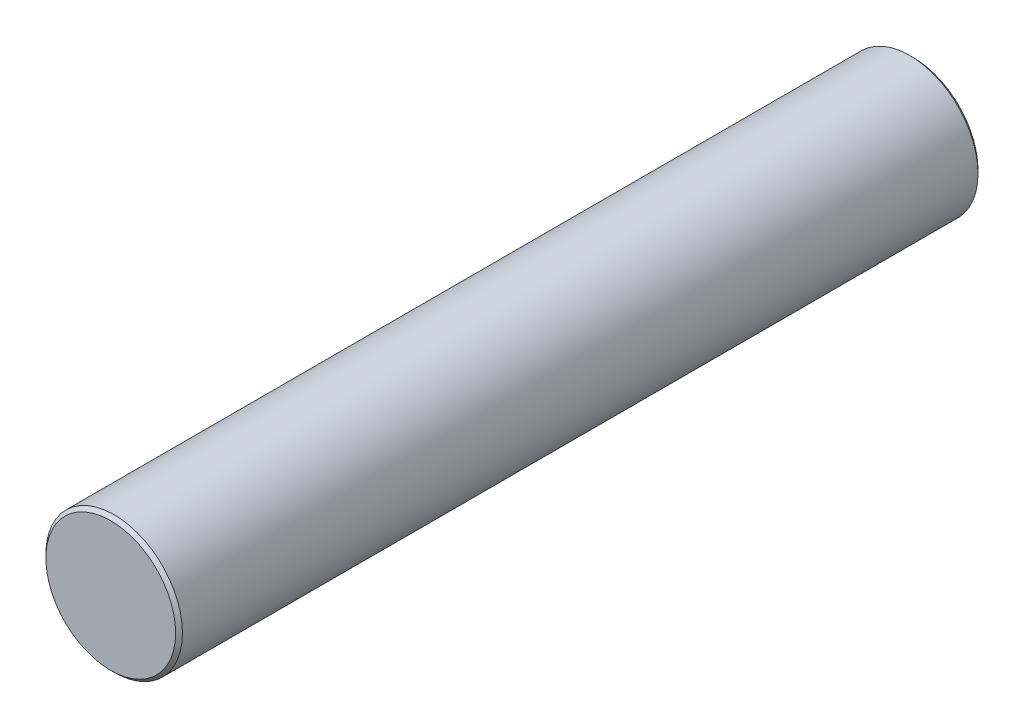
SolidWorks part; units mm, degrees
ref_plane "Front Plane" through (0, 0, 0) normal (0, 0, 1) x (1, 0, 0)
ref_plane "Top Plane" through (0, 0, 0) normal (0, 1, 0) x (1, 0, 0)
ref_plane "Right Plane" through (0, 0, 0) normal (1, 0, 0) x (0, 0, -1)
sketch "Sketch2" plane through (0, 0, 0) normal (0, 0, 1) x (1, 0, 0)
  circle A0 centre (0, 0) radius 1
  dimension "D1" = 2
extrude "Boss-Extrude1" add sketch "Sketch2" along normal blind 11.75
chamfer "Chamfer2" distance 0.05 angle 45 2 edges at (1, 0, 11.75) (1, 0, 0)
